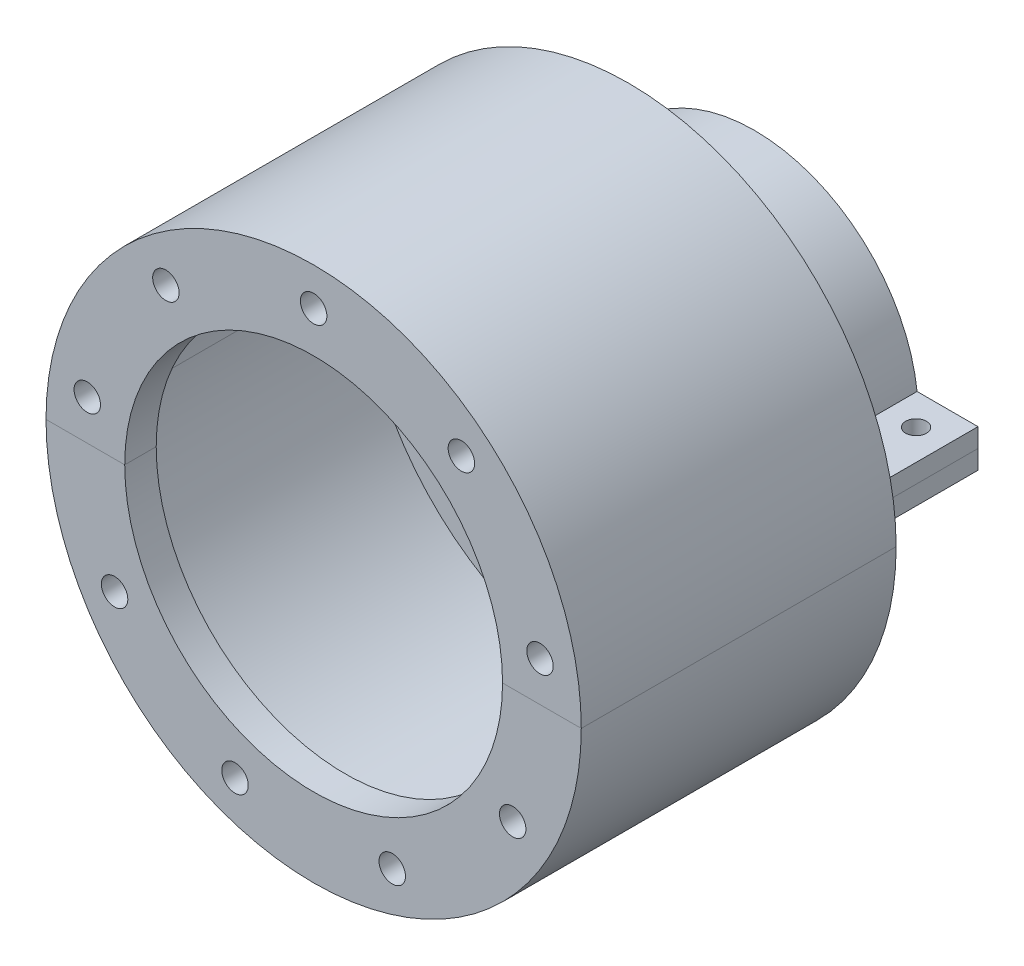
SolidWorks part; units mm, degrees
material "ABS"
ref_plane "正面" through (0, 0, 0) normal (0, 0, 1) x (1, 0, 0)
ref_plane "平面" through (0, 0, 0) normal (0, 1, 0) x (1, 0, 0)
ref_plane "右側面" through (0, 0, 0) normal (1, 0, 0) x (0, 0, -1)
sketch "ｽｹｯﾁ1" plane through (0, 0, 0) normal (0, 0, 1) x (1, 0, 0)
  circle A0 centre (0, 0) radius 42.5
  dimension "D1" = 85
extrude "ﾎﾞｽ - 押し出し1" add sketch "ｽｹｯﾁ1" along normal blind 3
sketch "ｽｹｯﾁ2" plane through (0, 0, 3) normal (0, 0, 1) x (1, 0, 0)
  circle A0 centre (0, 0) radius 42.5
  circle A1 centre (0, 0) radius 39.5
  dimension "D1" = 85
  dimension "D2" = 79
extrude "ﾎﾞｽ - 押し出し2" add sketch "ｽｹｯﾁ2" along normal blind 42
sketch "ｽｹｯﾁ3" plane through (0, 0, 45) normal (0, 0, 1) x (1, 0, 0)
  circle A0 centre (0, 0) radius 42.5
  circle A1 centre (0, 0) radius 30
  dimension "D1" = 60
  dimension "D2" = 85
extrude "ﾎﾞｽ - 押し出し3" add sketch "ｽｹｯﾁ3" along normal blind 5
sketch "ｽｹｯﾁ4" plane through (0, 0, 50) normal (0, 0, 1) x (1, 0, 0)
  line L0 (0, 0) -> (0, 42.5) construction
  circle A0 centre (0, 0) radius 42.5 construction
  circle A1 centre (0, 36.5) radius 2.1
  circle A2 centre (23.4617, 27.9606) radius 2.1
  circle A3 centre (35.9455, 6.3382) radius 2.1
  circle A4 centre (31.6099, -18.25) radius 2.1
  circle A5 centre (12.4837, -34.2988) radius 2.1
  circle A6 centre (-12.4837, -34.2988) radius 2.1
  circle A7 centre (-31.6099, -18.25) radius 2.1
  circle A8 centre (-35.9455, 6.3382) radius 2.1
  circle A9 centre (-23.4617, 27.9606) radius 2.1
  point P27 (0, 0)
  dimension "D2" = 4.2
  dimension "D1" = 36.5
  dimension "D3" = 9
extrude "ｶｯﾄ - 押し出し1" cut sketch "ｽｹｯﾁ4" against normal up to next
sketch "ｽｹｯﾁ5" plane through (0, 0, 0) normal (0, 0, -1) x (-1, 0, 0)
  circle A0 centre (0, 0) radius 23.1
  circle A1 centre (0, 0) radius 26
  dimension "D1" = 46.2
  dimension "D2" = 52
extrude "ﾎﾞｽ - 押し出し4" add sketch "ｽｹｯﾁ5" along normal blind 20
sketch "ｽｹｯﾁ6" plane through (0, 0, 0) normal (0, 1, 0) x (1, 0, 0)
  line L0 (26, 20) -> (-26, 20) construction
  line L1 (-24.5, 20) -> (-35.5, 20)
  line L2 (-24.5, 20) -> (-24.5, 0)
  line L3 (-24.5, 0) -> (-35.5, 0)
  line L4 (-35.5, 20) -> (-35.5, 0)
  line L5 (42.5, 0) -> (-42.5, 0) construction
  line L6 (0, 0) -> (0, 20) construction
  line L7 (23.1, 20) -> (-23.1, 20) construction
  line L8 (24.5, 0) -> (35.5, 0)
  line L9 (35.5, 20) -> (35.5, 0)
  line L10 (24.5, 20) -> (35.5, 20)
  line L11 (24.5, 20) -> (24.5, 0)
  dimension "D1" = 24.5
  dimension "D2" = 11
extrude "ﾎﾞｽ - 押し出し5" add sketch "ｽｹｯﾁ6" along normal blind 3 and the other way blind 3
sketch "ｽｹｯﾁ7" plane through (0, 3, 0) normal (0, 1, 0) x (1, 0, 0)
  line L0 (0, 0) -> (0, 20) construction
  line L1 (25.8263, 20) -> (-25.8263, 20) construction
  line L2 (-30.6632, 0) -> (-30.6632, 20) construction
  line L3 (-35.5, 0) -> (-25.8263, 0) construction
  line L4 (-25.8263, 20) -> (-35.5, 20) construction
  circle A0 centre (-30.6632, 15) radius 1.65
  circle A1 centre (-30.6632, 5) radius 1.65
  circle A2 centre (30.6632, 5) radius 1.65
  circle A3 centre (30.6632, 15) radius 1.65
  dimension "D3" = 3.3
  dimension "D1" = 5
  dimension "D2" = 5
extrude "ｶｯﾄ - 押し出し2" cut sketch "ｽｹｯﾁ7" against normal up to next
split "部品分割1" trim tools "平面" bodies to split 107 resulting bodies 108 109
